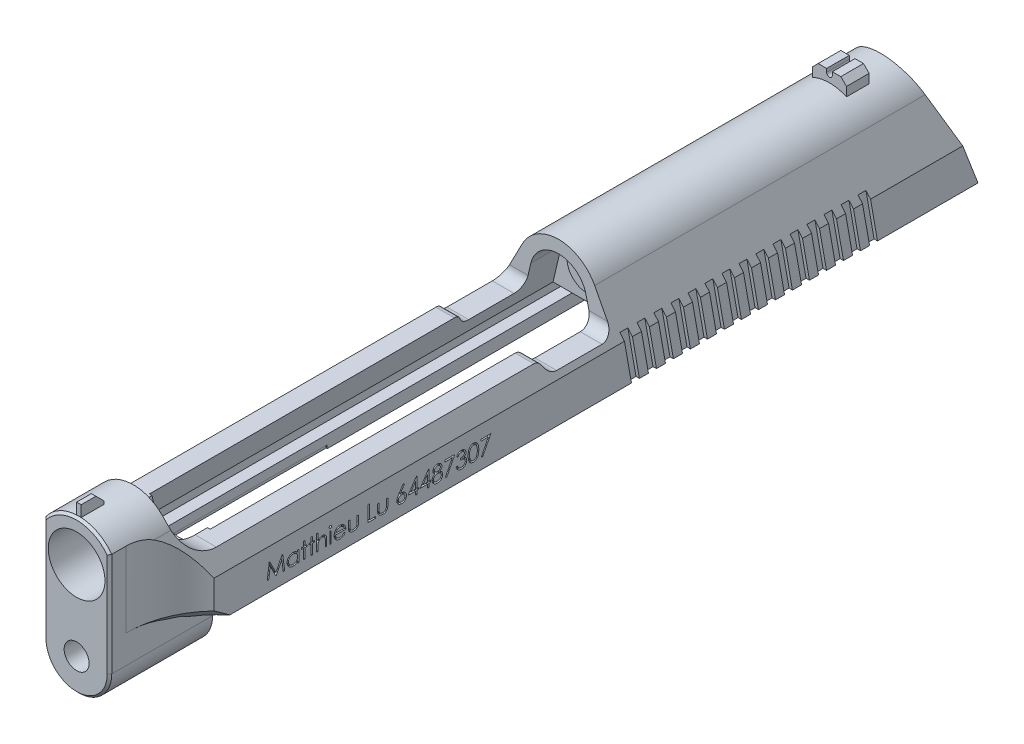
SolidWorks part; units mm, degrees
material "Cast Alloy Steel"
ref_plane "Front Plane" through (0, 0, 0) normal (0, 0, 1) x (1, 0, 0)
ref_plane "Top Plane" through (0, 0, 0) normal (0, 1, 0) x (1, 0, 0)
ref_plane "Right Plane" through (0, 0, 0) normal (1, 0, 0) x (0, 0, -1)
sketch "Sketch1" plane through (0, 0, 0) normal (0, 0, 1) x (1, 0, 0)
  line L0 (8.1106, 18.1927) -> (12.954, 8.89)
  line L1 (0, 0) -> (12.954, 0)
  line L2 (0, 0) -> (0, 23.114)
  line L3 (0, 23.114) -> (12.954, 23.114)
  line L4 (12.954, 0) -> (12.954, 23.114)
  line L6 (0, 0) -> (7.366, 0)
  line L7 (0, 0) -> (0, -11.176)
  line L8 (0, -11.176) -> (7.366, -11.176)
  line L9 (7.366, 0) -> (7.366, -11.176)
  circle A0 centre (0, 13.97) radius 9.144
  circle A1 centre (0, 13.97) radius 6.35
  circle A2 centre (0, -3.81) radius 2.794
  circle A3 centre (0, -3.81) radius 7.366
  dimension "D3" = 18.288
  dimension "D5" = 12.7
  dimension "D6" = 14.732
  dimension "D7" = 5.588
  dimension "D1" = 23.114
  dimension "D2" = 12.954
  dimension "D4" = 8.89
  dimension "D8" = 17.78
extrude "Boss-Extrude1" add sketch "Sketch1" against normal blind 188.976 contours A3 L6 L1 L4 L0 A0 L2 | L1 A3 L2 | A1 L2 A0 | L2 A1 region at (8.6108, 5.523, 0) region at (8.6833, 16.0951, 0) region at (2.695, 13.97, 0) region at (2.4644, 1.4567, 0)
extrude "Boss-Extrude2" add sketch "Sketch1<4>" against normal blind 23.114 contours A3 L9 L6 | A3 L1 L7 A2 region at (7.0518, -0.9382, 0) region at (3.7266, -5.2723, 0)
sketch "Sketch1<4>" plane through (0, 0, 0) normal (0, 0, 1) x (1, 0, 0) same geometry as "Sketch1"
sketch "Sketch2" plane through (0, 0, 0) normal (-1, 0, 0) x (0, 0, 1)
  line L0 (-188.976, 23.114) -> (0, 23.114) construction
  line L1 (-12.7, 23.114) -> (-107.95, 23.114)
  line L2 (-12.7, 23.114) -> (-12.7, 12.7)
  line L3 (-12.7, 12.7) -> (-107.95, 12.7)
  line L4 (-107.95, 23.114) -> (-107.95, 12.7)
  line L5 (-107.95, 12.7) -> (-109.7863, 23.114)
  line L6 (0, -1.016) -> (0, 23.114) construction
  line L7 (-109.7863, 23.114) -> (-107.95, 23.114)
  line L8 (-107.95, 12.7) -> (-95.25, 12.7)
  line L9 (-107.95, 12.7) -> (-107.95, 10.16)
  line L10 (-107.95, 10.16) -> (-95.25, 10.16)
  line L11 (-95.25, 12.7) -> (-95.25, 10.16)
  circle A0 centre (-23.114, 23.114) radius 10.414
  arc A2 (-95.25, 10.16) -> (-92.9274, 11.7084) centre (-95.25, 12.6762) ccw
  arc A3 (-91.44, 12.7) -> (-92.9274, 11.7084) centre (-91.44, 11.0887) ccw
  dimension "D1" = 12.7
  dimension "D2" = 95.25
  dimension "D3" = 10.414
  dimension "D4" = 2.54
  dimension "D5" = 12.7
  dimension "D6" = 3.81
  dimension "D7" = 10
extrude "Cut-Extrude1" cut sketch "Sketch2" against normal through all contours L1 A0 | A0 L1 L4 L3 | L8 L9 L10 | L3 | L11 L3 region at (0, 18.6942, -23.114) region at (0, 15.0262, -15.0262) region at (0, 17.823, -69.5863) region at (0, 11.6661, -94.0895) region at (0, 11.43, -101.6)
sketch "Sketch3" plane through (0, 12.7, 0) normal (0, 1, 0) x (1, 0, 0)
  line L0 (0, 107.95) -> (0, 95.25) construction
  line L1 (0, 107.95) -> (6.35, 107.95)
  line L2 (0, 107.95) -> (0, 23.114)
  line L3 (0, 23.114) -> (6.35, 23.114)
  line L4 (6.35, 107.95) -> (6.35, 23.114)
  dimension "D1" = 6.35
extrude "Cut-Extrude2" cut sketch "Sketch3" against normal up to surface (12.7 mm away) up to face at (6.7733, 0, -70.6967)
extrude "Cut-Extrude3" cut sketch "Sketch1<5>" against normal blind 114.808 contours L2 A1 region at (2.695, 13.97, 0)
sketch "Sketch1<5>" plane through (0, 0, 0) normal (0, 0, 1) x (1, 0, 0) same geometry as "Sketch1"
sketch3d "3DSketch1" plane through (0, 0, 0) normal (0, 0, 1) x (1, 0, 0)
sketch "Sketch5" plane through (0, 0, -188.976) normal (0, 0, 1) x (1, 0, 0)
  line L0 (12.954, 0) -> (12.954, 2.794)
  line L1 (12.954, 0) -> (8.382, 0)
  line L2 (12.954, 0) -> (12.954, 2.794)
  line L3 (12.954, 2.794) -> (8.382, 2.794)
  line L4 (8.382, 0) -> (8.382, 2.794)
  line L5 (8.382, 2.794) -> (10.922, 2.794)
  line L6 (8.382, 2.794) -> (8.382, 7.366)
  line L7 (8.382, 7.366) -> (10.922, 7.366)
  line L8 (10.922, 2.794) -> (10.922, 7.366)
  line L9 (8.382, 7.366) -> (0, 7.366)
  line L10 (8.382, 7.366) -> (8.382, 0)
  line L11 (8.382, 0) -> (0, 0)
  line L12 (0, 7.366) -> (0, 0)
  line L13 (0, 0) -> (0, 23.114) construction
  line L15 (4.572, 7.366) -> (0, 7.366)
  line L16 (4.572, 7.366) -> (4.572, 32.766)
  line L17 (4.572, 32.766) -> (0, 32.766)
  line L18 (0, 7.366) -> (0, 32.766)
  dimension "D1" = 2.794
  dimension "D2" = 4.572
  dimension "D3" = 4.572
  dimension "D4" = 2.54
  dimension "D5" = 25.4
  dimension "D6" = 4.572
extrude "SlideCut" cut sketch "Sketch5" along normal up to surface (165.862 mm away) contours L9 L12 L11 L4 L6 | L3 L8 L7 L6 region at (4.191, 3.683, -188.976) region at (9.652, 5.08, -188.976) up to face at (4.3198, 0.8644, -23.114)
sketch "Sketch6" plane through (12.954, 0, 0) normal (1, 0, 0) x (0, 0, -1)
  line L0 (188.976, 0) -> (180.1034, 23.114)
  line L1 (188.976, 23.114) -> (107.95, 23.114) construction
  line L2 (188.976, 0) -> (0, 0) construction
  dimension "D1" = 69
extrude "Cut-Extrude6" cut sketch "Sketch6" against normal through all and the other way through all flip side to cut
sketch "Sketch7" plane through (0, 0, -114.808) normal (0, 0, 1) x (1, 0, 0)
  line L0 (0, 13.7724) -> (0, 33.6913) construction
  line L1 (0, 1.016) -> (6.096, 1.016)
  line L2 (0, 7.4611) -> (0, 1.016)
  line L3 (8.128, 7.1684) -> (0, 7.1684)
  line L4 (0, 1.016) -> (6.096, 1.016)
  line L5 (0, 7.62) -> (0, 1.016)
  line L6 (0, 1.016) -> (0, 3.1044)
  line L7 (0, 3.1044) -> (4.572, 3.1044)
  line L8 (0, 5.3904) -> (4.572, 5.3904)
  line L9 (0, 3.1044) -> (0, 5.3904)
  line L10 (8.128, 7.1684) -> (6.1805, 15.4274)
  line L11 (4.572, 3.1044) -> (4.572, 5.3904)
  line L12 (6.096, 1.016) -> (6.096, 3.302)
  line L13 (0, 20.32) -> (0, 23.114) construction
  line L14 (0, 3.1044) -> (6.096, 3.302)
  arc A0 (8.128, 7.1684) -> (4.572, 5.3904) centre (4.1364, 10.7065) cw
  arc A1 (0, 7.62) -> (0, 20.32) centre (0, 13.97) ccw construction
  circle A3 centre (0, 13.97) radius 6.35
  point P18 (0, 7.1684)
  line M3 (0, 20.32) -> (0, 7.62)
  arc M4 (0, 7.62) -> (0, 20.32) centre (0, 13.97) ccw
  dimension "D6" = 5.334
  dimension "D7" = 12.954
  dimension "D1" = 2.286
  dimension "D2" = 2.286
  dimension "D3" = 6.096
  dimension "D4" = 4.572
  dimension "D5" = 8.128
extrude "Cut-Extrude8" cut sketch "Sketch7" along normal up to surface (91.694 mm away) contours L3 L10 L5 L2 M4 | A0 L3 L2 L8 | L5 L14 L11 L8 | L14 L11 L7 L5 L1 L12 | M4 M3 region at (3.0951, 2.0831, -114.808) region at (2.2605, 4.284, -114.808) region at (3.5213, 6.3439, -114.808) region at (5.3959, 9.0228, -114.808) region at (2.695, 13.97, -114.808) up to face at (5.9605, 2.1615, -23.114)
sketch "Sketch10" plane through (0, 0, -114.808) normal (0, 0, 1) x (1, 0, 0)
  circle A0 centre (0, 13.97) radius 4.445
  arc A1 (0, 7.62) -> (0, 20.32) centre (0, 13.97) ccw construction
  line M2 (0, 20.32) -> (0, 7.366)
  dimension "D1" = 8.89
extrude "Boss-Extrude3" add sketch "Sketch10" along normal blind 0.508 contours A0 M2 region at (1.8865, 13.97, -114.808)
sketch "Sketch11" plane through (0, 0, 0) normal (0, -1, 0) x (1, 0, 0)
  line L1 (7.366, -3.7442) -> (7.366, 0)
  line L3 (7.366, -23.114) -> (7.366, 0) construction
  line L4 (12.954, -188.976) -> (12.954, 0) construction
  arc A1 (7.366, -3.7442) -> (12.954, -17.8375) centre (27.9322, -3.7442) ccw
  line M4 (12.954, -188.976) -> (12.954, 0)
  line M5 (12.954, 0) -> (7.366, 0)
  line M6 (7.366, 0) -> (7.366, -23.114)
extrude "Cut-Extrude11" cut sketch "Sketch11" against normal through all contours A1 M6 M4 M5 region at (10.5426, 0, -7.1137)
sketch "Sketch12" plane through (0, 0, 0) normal (0, 0, 1) x (1, 0, 0)
  line L1 (7.366, 0) -> (8.636, 0)
  line L2 (7.366, 0) -> (7.366, 0.762)
  line L3 (7.366, 0.762) -> (8.636, 0.762)
  line L4 (8.636, 0) -> (8.636, 0.762)
  dimension "D1" = 1.27
  dimension "D2" = 0.762
extrude "Cut-Extrude12" cut sketch "Sketch12" against normal blind 64.516
fillet "Fillet2" radius 7.62 1 edges at (7.82, 12.7, -12.7)
chamfer "Chamfer1" distance 2.54 1 edges at (10.4434, 0, -14.566)
chamfer "Chamfer2" distance 0.508 angle 45 3 edges at (4.1274, 22.1295, 0) (7.366, 7.789, 0) (5.2085, -9.0185, 0)
fillet "Fillet3" radius 2.54 1 edges at (9.8577, 10.16, -107.95)
sketch "Sketch13" plane through (12.954, 0, 0) normal (1, 0, 0) x (0, 0, -1)
  line L0 (113.1229, 0) -> (108.6441, 25.4)
  line L1 (188.976, 0) -> (21.3382, 0) construction
  line L2 (108.6441, 25.4) -> (106.8661, 25.4)
  line L3 (106.8661, 25.4) -> (111.3449, 0)
  line L4 (111.3449, 0) -> (113.1229, 0)
  line L5 (115.1549, 0) -> (116.9329, 0)
  line L6 (116.9329, 0) -> (112.4541, 25.4)
  line L7 (112.4541, 25.4) -> (110.6761, 25.4)
  line L8 (110.6761, 25.4) -> (115.1549, 0)
  line L9 (118.9649, 0) -> (120.7429, 0)
  line L10 (120.7429, 0) -> (116.2641, 25.4)
  line L11 (116.2641, 25.4) -> (114.4861, 25.4)
  line L12 (114.4861, 25.4) -> (118.9649, 0)
  line L13 (122.7749, 0) -> (124.5529, 0)
  line L14 (124.5529, 0) -> (120.0741, 25.4)
  line L15 (120.0741, 25.4) -> (118.2961, 25.4)
  line L16 (118.2961, 25.4) -> (122.7749, 0)
  line L17 (126.5849, 0) -> (128.3629, 0)
  line L18 (128.3629, 0) -> (123.8841, 25.4)
  line L19 (123.8841, 25.4) -> (122.1061, 25.4)
  line L20 (122.1061, 25.4) -> (126.5849, 0)
  line L21 (130.3949, 0) -> (132.1729, 0)
  line L22 (132.1729, 0) -> (127.6941, 25.4)
  line L23 (127.6941, 25.4) -> (125.9161, 25.4)
  line L24 (125.9161, 25.4) -> (130.3949, 0)
  line L25 (134.2049, 0) -> (135.9829, 0)
  line L26 (135.9829, 0) -> (131.5041, 25.4)
  line L27 (131.5041, 25.4) -> (129.7261, 25.4)
  line L28 (129.7261, 25.4) -> (134.2049, 0)
  line L29 (138.0149, 0) -> (139.7929, 0)
  line L30 (139.7929, 0) -> (135.3141, 25.4)
  line L31 (135.3141, 25.4) -> (133.5361, 25.4)
  line L32 (133.5361, 25.4) -> (138.0149, 0)
  line L33 (141.8249, 0) -> (143.6029, 0)
  line L34 (143.6029, 0) -> (139.1241, 25.4)
  line L35 (139.1241, 25.4) -> (137.3461, 25.4)
  line L36 (137.3461, 25.4) -> (141.8249, 0)
  line L37 (145.6349, 0) -> (147.4129, 0)
  line L38 (147.4129, 0) -> (142.9341, 25.4)
  line L39 (142.9341, 25.4) -> (141.1561, 25.4)
  line L40 (141.1561, 25.4) -> (145.6349, 0)
  line L41 (149.4449, 0) -> (151.2229, 0)
  line L42 (151.2229, 0) -> (146.7441, 25.4)
  line L43 (146.7441, 25.4) -> (144.9661, 25.4)
  line L44 (144.9661, 25.4) -> (149.4449, 0)
  line L45 (153.2549, 0) -> (155.0329, 0)
  line L46 (155.0329, 0) -> (150.5541, 25.4)
  line L47 (150.5541, 25.4) -> (148.7761, 25.4)
  line L48 (148.7761, 25.4) -> (153.2549, 0)
  line L49 (157.0649, 0) -> (158.8429, 0)
  line L50 (158.8429, 0) -> (154.3641, 25.4)
  line L51 (154.3641, 25.4) -> (152.5861, 25.4)
  line L52 (152.5861, 25.4) -> (157.0649, 0)
  line L53 (160.8749, 0) -> (162.6529, 0)
  line L54 (162.6529, 0) -> (158.1741, 25.4)
  line L55 (158.1741, 25.4) -> (156.3961, 25.4)
  line L56 (156.3961, 25.4) -> (160.8749, 0)
  line L57 (164.6849, 0) -> (166.4629, 0)
  line L58 (166.4629, 0) -> (161.9841, 25.4)
  line L59 (161.9841, 25.4) -> (160.2061, 25.4)
  line L60 (160.2061, 25.4) -> (164.6849, 0)
  dimension "D1" = 25.4
  dimension "D2" = 80
  dimension "D3" = 1.778
  dimension "D4" = 15
extrude "Cut-Extrude13" cut sketch "Sketch13" against normal blind 0.762
sketch "Sketch14" plane through (0, 0, -188.976) normal (0, 0, 1) x (1, 0, 0)
  line L1 (3.81, 22.2824) -> (0, 22.2824)
  line L2 (3.81, 22.2824) -> (3.81, 25.5844)
  line L3 (3.81, 25.5844) -> (0, 25.5844)
  line L4 (0, 22.2824) -> (0, 25.5844)
  line L5 (2.54, 25.5844) -> (3.81, 24.3144)
  line L6 (0.635, 24.8224) -> (0.635, 25.5844)
  line L7 (0, 23.114) -> (0, 7.366) construction
  circle A1 centre (0, 24.8224) radius 0.635
  arc A2 (8.1106, 18.1927) -> (0, 23.114) centre (0, 13.97) ccw construction
  dimension "D5" = 1.27
  dimension "D1" = 3.81
  dimension "D2" = 3.302
  dimension "D3" = 45
  dimension "D4" = 1.27
  dimension "D6" = 0.762
extrude "Boss-Extrude4" add sketch "Sketch14" along normal blind 5.08 from offset 15.24 contours A1 L4 L1 L2 L5 L3 L6 region at (1.9133, 23.7693, -188.976)
sketch "Sketch15" plane through (0, 0, 0) normal (0, 0, 1) x (1, 0, 0)
  line L0 (2.54, 25.5844) -> (0.635, 25.5844) construction
  line L1 (0, 22.606) -> (0.508, 22.606)
  line L2 (0, 22.606) -> (0, 25.5844)
  line L3 (0, 25.5844) -> (0.508, 25.5844)
  line L4 (0.508, 22.606) -> (0.508, 25.5844)
  dimension "D1" = 0.508
extrude "Boss-Extrude5" add sketch "Sketch15" against normal blind 5.08 from vertex starting at point (0, 23.114, -0.508)
fillet "Chamfer3" radius 1.778 1 edges at (0.254, 25.5844, -5.588) type face fillet profile chamfer first side face at (0.254, 25.5844, -3.048) second side face at (0.254, 24.3466, -5.588)
sketch "Sketch19" plane through (0, 0, -114.808) normal (0, 0, 1) x (1, 0, 0)
  line L0 (8.0814, 7.366) -> (0, 7.366) construction
  line L1 (0, 9.525) -> (7.5723, 9.525)
  line L2 (0, 9.525) -> (0, 7.366)
  line L3 (0, 7.366) -> (7.5723, 7.366)
  line L4 (7.5723, 9.525) -> (7.5723, 7.366)
  line L5 (8.0814, 7.366) -> (6.1805, 15.4274) construction
  line L6 (7.5723, 9.525) -> (8.0814, 7.366)
  line L7 (8.0814, 7.366) -> (7.5723, 7.366)
sketch "Sketch20" plane through (0, 0, -114.3) normal (0, 0, 1) x (1, 0, 0)
  line L0 (0, 18.415) -> (0, 9.525) construction
  circle A0 centre (0, 13.97) radius 0.635
  dimension "D1" = 1.27
extrude "Cut-Extrude18" cut sketch "Sketch20" against normal up to surface (74.676 mm away)
sketch "Sketch21" plane through (0, 0, -188.976) normal (0, 0, 1) x (1, 0, 0)
  line L1 (0, 7.366) -> (4.572, 7.366)
  line L2 (0, 7.366) -> (0, 17.78)
  line L3 (0, 17.78) -> (4.572, 17.78)
  line L4 (4.572, 7.366) -> (4.572, 17.78)
  dimension "D1" = 10.414
  dimension "D2" = 4.572
extrude "Cut-Extrude20" cut sketch "Sketch21" along normal blind 11.684 from vertex starting at point (0, 7.366, -186.1485)
fillet "Fillet6" radius 1.524 1 edges at (2.286, 17.78, -174.4645)
mirror "Mirror1" about plane through (0, 0, -188.976) normal (1, 0, 0) of bodies 134
sketch "Sketch22" plane through (12.954, 0, 0) normal (1, 0, 0) x (0, 0, -1)
  text T0 "Matthieu Lu 64487307"
extrude "Cut-Extrude21" cut sketch "Sketch22" against normal blind 0.508
